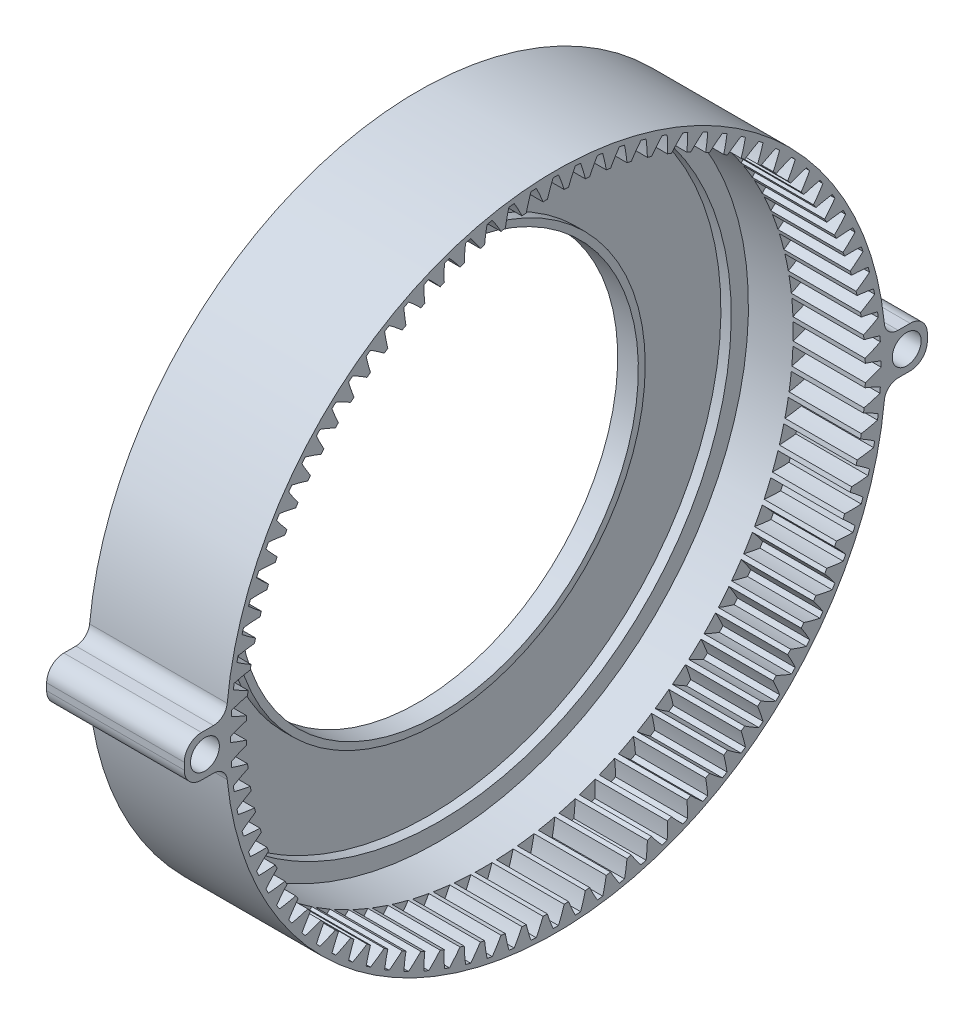
SolidWorks part; units mm, degrees
ref_plane "Front Plane" through (0, 0, 0) normal (0, 0, 1) x (1, 0, 0)
ref_plane "Top Plane" through (0, 0, 0) normal (0, 1, 0) x (1, 0, 0)
ref_plane "Right Plane" through (0, 0, 0) normal (1, 0, 0) x (0, 0, -1)
ref_plane "Plane1" through (0, 0, 0) normal (0, 0, -1) x (-1, 0, 0)
sketch "Sketch1" plane through (0, 0, 0) normal (0, 0, -1) x (-1, 0, 0)
  line L0 (-20, 48) -> (-20, 0)
  line L1 (-20, 0) -> (0, 0)
  line L2 (0, 0) -> (0, 48)
  line L3 (0, 48) -> (-20, 48)
  line L4 (-20, 0) -> (0, 0) construction
  dimension "D1" = 48
  dimension "D2" = 20
revolve "Revolve1" add sketch "Sketch1" angle 360 about L4 reverse direction yes
sketch "Sketch2" plane through (20, 0, 0) normal (1, 0, 0) x (0, 0, -1)
  arc A0 (-4.9202, -44.7302) -> (-4.2833, -44.7957) centre (0, 0) ccw
  arc A1 (-4.2833, -44.7957) -> (-3.6099, -47.1129) centre (18.1092, -39.5446) ccw
  arc A2 (-3.6099, -47.1129) -> (-2.8389, -47.1656) centre (0, 0) ccw
  arc A3 (-2.8389, -47.1656) -> (-1.8563, -44.9617) centre (-23.3252, -36.7104) ccw
  arc A4 (-1.8563, -44.9617) -> (-1.2163, -44.9836) centre (0, 0) ccw
  arc A5 (-1.2163, -44.9836) -> (-0.3864, -47.2494) centre (20.7656, -38.2166) ccw
  arc A6 (-0.3864, -47.2494) -> (0.3864, -47.2494) centre (0, 0) ccw
  arc A7 (0.3864, -47.2494) -> (1.2163, -44.9836) centre (-20.7656, -38.2166) ccw
  arc A8 (1.2163, -44.9836) -> (1.8563, -44.9617) centre (0, 0) ccw
  arc A9 (1.8563, -44.9617) -> (2.8389, -47.1656) centre (23.3252, -36.7104) ccw
  arc A10 (2.8389, -47.1656) -> (3.6099, -47.1129) centre (0, 0) ccw
  arc A11 (3.6099, -47.1129) -> (4.2833, -44.7957) centre (-18.1092, -39.5446) ccw
  arc A12 (4.2833, -44.7957) -> (4.9202, -44.7302) centre (0, 0) ccw
  arc A13 (4.9202, -44.7302) -> (6.051, -46.8619) centre (25.7761, -35.0331) ccw
  arc A14 (6.051, -46.8619) -> (6.8166, -46.7567) centre (0, 0) ccw
  arc A15 (6.8166, -46.7567) -> (7.3303, -44.399) centre (-15.3684, -40.6882) ccw
  arc A16 (7.3303, -44.399) -> (7.9613, -44.2902) centre (0, 0) ccw
  arc A17 (7.9613, -44.2902) -> (9.2349, -46.3398) centre (28.1067, -33.1924) ccw
  arc A18 (9.2349, -46.3398) -> (9.9915, -46.1825) centre (0, 0) ccw
  arc A19 (9.9915, -46.1825) -> (10.3431, -43.7952) centre (-12.5559, -41.6422) ccw
  arc A20 (10.3431, -43.7952) -> (10.9652, -43.6436) centre (0, 0) ccw
  arc A21 (10.9652, -43.6436) -> (12.3757, -45.6015) centre (30.3063, -31.1969) ccw
  arc A22 (12.3757, -45.6015) -> (13.1198, -45.393) centre (0, 0) ccw
  arc A23 (13.1198, -45.393) -> (13.3077, -42.9873) centre (-9.6849, -42.4019) ccw
  arc A24 (13.3077, -42.9873) -> (13.918, -42.7936) centre (0, 0) ccw
  arc A25 (13.918, -42.7936) -> (15.4588, -44.6507) centre (32.3646, -29.056) ccw
  arc A26 (15.4588, -44.6507) -> (16.1869, -44.3919) centre (0, 0) ccw
  arc A27 (16.1869, -44.3919) -> (16.2102, -41.9789) centre (-6.7687, -42.964) ccw
  arc A28 (16.2102, -41.9789) -> (16.8058, -41.744) centre (0, 0) ccw
  arc A29 (16.8058, -41.744) -> (18.4698, -43.4916) centre (34.272, -26.7796) ccw
  arc A30 (18.4698, -43.4916) -> (19.1786, -43.1838) centre (0, 0) ccw
  arc A31 (19.1786, -43.1838) -> (19.0371, -40.7748) centre (-3.821, -43.3257) ccw
  arc A32 (19.0371, -40.7748) -> (19.6154, -40.4998) centre (0, 0) ccw
  arc A33 (19.6154, -40.4998) -> (21.3948, -42.1298) centre (36.0196, -24.3784) ccw
  arc A34 (21.3948, -42.1298) -> (22.0809, -41.7743) centre (0, 0) ccw
  arc A35 (22.0809, -41.7743) -> (21.7753, -39.3806) centre (-0.8554, -43.4855) ccw
  arc A36 (21.7753, -39.3806) -> (22.3335, -39.0668) centre (0, 0) ccw
  arc A37 (22.3335, -39.0668) -> (24.2199, -40.5716) centre (37.5993, -21.8635) ccw
  arc A38 (24.2199, -40.5716) -> (24.8802, -40.1701) centre (0, 0) ccw
  arc A39 (24.8802, -40.1701) -> (24.412, -37.8028) centre (2.1142, -43.4425) ccw
  arc A40 (24.412, -37.8028) -> (24.9474, -37.4517) centre (0, 0) ccw
  arc A41 (24.9474, -37.4517) -> (26.9322, -38.8242) centre (39.0037, -19.2467) ccw
  arc A42 (26.9322, -38.8242) -> (27.5635, -38.3785) centre (0, 0) ccw
  arc A43 (27.5635, -38.3785) -> (26.9349, -36.0488) centre (5.0738, -43.1969) ccw
  arc A44 (26.9349, -36.0488) -> (27.445, -35.6619) centre (0, 0) ccw
  arc A45 (27.445, -35.6619) -> (29.5188, -36.8957) centre (40.2262, -16.5401) ccw
  arc A46 (29.5188, -36.8957) -> (30.1183, -36.4081) centre (0, 0) ccw
  arc A47 (30.1183, -36.4081) -> (29.3321, -34.1266) centre (8.0099, -42.75) ccw
  arc A48 (29.3321, -34.1266) -> (29.8147, -33.7058) centre (0, 0) ccw
  arc A49 (29.8147, -33.7058) -> (31.9679, -34.7953) centre (41.2611, -13.7564) ccw
  arc A50 (31.9679, -34.7953) -> (32.5326, -34.2679) centre (0, 0) ccw
  arc A51 (32.5326, -34.2679) -> (31.5926, -32.0454) centre (10.9086, -42.1037) ccw
  arc A52 (31.5926, -32.0454) -> (32.0454, -31.5926) centre (0, 0) ccw
  arc A53 (32.0454, -31.5926) -> (34.2679, -32.5326) centre (42.1037, -10.9086) ccw
  arc A54 (34.2679, -32.5326) -> (34.7953, -31.9679) centre (0, 0) ccw
  arc A55 (34.7953, -31.9679) -> (33.7058, -29.8147) centre (13.7564, -41.2611) ccw
  arc A56 (33.7058, -29.8147) -> (34.1266, -29.3321) centre (0, 0) ccw
  arc A57 (34.1266, -29.3321) -> (36.4081, -30.1183) centre (42.75, -8.0099) ccw
  arc A58 (36.4081, -30.1183) -> (36.8957, -29.5188) centre (0, 0) ccw
  arc A59 (36.8957, -29.5188) -> (35.6619, -27.445) centre (16.5401, -40.2262) ccw
  arc A60 (35.6619, -27.445) -> (36.0488, -26.9349) centre (0, 0) ccw
  arc A61 (36.0488, -26.9349) -> (38.3785, -27.5635) centre (43.1969, -5.0738) ccw
  arc A62 (38.3785, -27.5635) -> (38.8242, -26.9322) centre (0, 0) ccw
  arc A63 (38.8242, -26.9322) -> (37.4517, -24.9474) centre (19.2467, -39.0037) ccw
  arc A64 (37.4517, -24.9474) -> (37.8028, -24.412) centre (0, 0) ccw
  arc A65 (37.8028, -24.412) -> (40.1701, -24.8802) centre (43.4425, -2.1142) ccw
  arc A66 (40.1701, -24.8802) -> (40.5716, -24.2199) centre (0, 0) ccw
  arc A67 (40.5716, -24.2199) -> (39.0668, -22.3335) centre (21.8635, -37.5993) ccw
  arc A68 (39.0668, -22.3335) -> (39.3806, -21.7753) centre (0, 0) ccw
  arc A69 (39.3806, -21.7753) -> (41.7743, -22.0809) centre (43.4855, 0.8554) ccw
  arc A70 (41.7743, -22.0809) -> (42.1298, -21.3948) centre (0, 0) ccw
  arc A71 (42.1298, -21.3948) -> (40.4998, -19.6154) centre (24.3784, -36.0196) ccw
  arc A72 (40.4998, -19.6154) -> (40.7748, -19.0371) centre (0, 0) ccw
  arc A73 (40.7748, -19.0371) -> (43.1838, -19.1786) centre (43.3257, 3.821) ccw
  arc A74 (43.1838, -19.1786) -> (43.4916, -18.4698) centre (0, 0) ccw
  arc A75 (43.4916, -18.4698) -> (41.744, -16.8058) centre (26.7796, -34.272) ccw
  arc A76 (41.744, -16.8058) -> (41.9789, -16.2102) centre (0, 0) ccw
  arc A77 (41.9789, -16.2102) -> (44.3919, -16.1869) centre (42.964, 6.7687) ccw
  arc A78 (44.3919, -16.1869) -> (44.6507, -15.4588) centre (0, 0) ccw
  arc A79 (44.6507, -15.4588) -> (42.7936, -13.918) centre (29.056, -32.3646) ccw
  arc A80 (42.7936, -13.918) -> (42.9873, -13.3077) centre (0, 0) ccw
  arc A81 (42.9873, -13.3077) -> (45.393, -13.1198) centre (42.4019, 9.6849) ccw
  arc A82 (45.393, -13.1198) -> (45.6015, -12.3757) centre (0, 0) ccw
  arc A83 (45.6015, -12.3757) -> (43.6436, -10.9652) centre (31.1969, -30.3063) ccw
  arc A84 (43.6436, -10.9652) -> (43.7952, -10.3431) centre (0, 0) ccw
  arc A85 (43.7952, -10.3431) -> (46.1825, -9.9915) centre (41.6422, 12.5559) ccw
  arc A86 (46.1825, -9.9915) -> (46.3398, -9.2349) centre (0, 0) ccw
  arc A87 (46.3398, -9.2349) -> (44.2902, -7.9613) centre (33.1924, -28.1067) ccw
  arc A88 (44.2902, -7.9613) -> (44.399, -7.3303) centre (0, 0) ccw
  arc A89 (44.399, -7.3303) -> (46.7567, -6.8166) centre (40.6882, 15.3684) ccw
  arc A90 (46.7567, -6.8166) -> (46.8619, -6.051) centre (0, 0) ccw
  arc A91 (46.8619, -6.051) -> (44.7302, -4.9202) centre (35.0331, -25.7761) ccw
  arc A92 (44.7302, -4.9202) -> (44.7957, -4.2833) centre (0, 0) ccw
  arc A93 (44.7957, -4.2833) -> (47.1129, -3.6099) centre (39.5446, 18.1092) ccw
  arc A94 (47.1129, -3.6099) -> (47.1656, -2.8389) centre (0, 0) ccw
  arc A95 (47.1656, -2.8389) -> (44.9617, -1.8563) centre (36.7104, -23.3252) ccw
  arc A96 (44.9617, -1.8563) -> (44.9836, -1.2163) centre (0, 0) ccw
  arc A97 (44.9836, -1.2163) -> (47.2494, -0.3864) centre (38.2166, 20.7656) ccw
  arc A98 (47.2494, -0.3864) -> (47.2494, 0.3864) centre (0, 0) ccw
  arc A99 (47.2494, 0.3864) -> (44.9836, 1.2163) centre (38.2166, -20.7656) ccw
  arc A100 (44.9836, 1.2163) -> (44.9617, 1.8563) centre (0, 0) ccw
  arc A101 (44.9617, 1.8563) -> (47.1656, 2.8389) centre (36.7104, 23.3252) ccw
  arc A102 (47.1656, 2.8389) -> (47.1129, 3.6099) centre (0, 0) ccw
  arc A103 (47.1129, 3.6099) -> (44.7957, 4.2833) centre (39.5446, -18.1092) ccw
  arc A104 (44.7957, 4.2833) -> (44.7302, 4.9202) centre (0, 0) ccw
  arc A105 (44.7302, 4.9202) -> (46.8619, 6.051) centre (35.0331, 25.7761) ccw
  arc A106 (46.8619, 6.051) -> (46.7567, 6.8166) centre (0, 0) ccw
  arc A107 (46.7567, 6.8166) -> (44.399, 7.3303) centre (40.6882, -15.3684) ccw
  arc A108 (44.399, 7.3303) -> (44.2902, 7.9613) centre (0, 0) ccw
  arc A109 (44.2902, 7.9613) -> (46.3398, 9.2349) centre (33.1924, 28.1067) ccw
  arc A110 (46.3398, 9.2349) -> (46.1825, 9.9915) centre (0, 0) ccw
  arc A111 (46.1825, 9.9915) -> (43.7952, 10.3431) centre (41.6422, -12.5559) ccw
  arc A112 (43.7952, 10.3431) -> (43.6436, 10.9652) centre (0, 0) ccw
  arc A113 (43.6436, 10.9652) -> (45.6015, 12.3757) centre (31.1969, 30.3063) ccw
  arc A114 (45.6015, 12.3757) -> (45.393, 13.1198) centre (0, 0) ccw
  arc A115 (45.393, 13.1198) -> (42.9873, 13.3077) centre (42.4019, -9.6849) ccw
  arc A116 (42.9873, 13.3077) -> (42.7936, 13.918) centre (0, 0) ccw
  arc A117 (42.7936, 13.918) -> (44.6507, 15.4588) centre (29.056, 32.3646) ccw
  arc A118 (44.6507, 15.4588) -> (44.3919, 16.1869) centre (0, 0) ccw
  arc A119 (44.3919, 16.1869) -> (41.9789, 16.2102) centre (42.964, -6.7687) ccw
  arc A120 (41.9789, 16.2102) -> (41.744, 16.8058) centre (0, 0) ccw
  arc A121 (41.744, 16.8058) -> (43.4916, 18.4698) centre (26.7796, 34.272) ccw
  arc A122 (43.4916, 18.4698) -> (43.1838, 19.1786) centre (0, 0) ccw
  arc A123 (43.1838, 19.1786) -> (40.7748, 19.0371) centre (43.3257, -3.821) ccw
  arc A124 (40.7748, 19.0371) -> (40.4998, 19.6154) centre (0, 0) ccw
  arc A125 (40.4998, 19.6154) -> (42.1298, 21.3948) centre (24.3784, 36.0196) ccw
  arc A126 (42.1298, 21.3948) -> (41.7743, 22.0809) centre (0, 0) ccw
  arc A127 (41.7743, 22.0809) -> (39.3806, 21.7753) centre (43.4855, -0.8554) ccw
  arc A128 (39.3806, 21.7753) -> (39.0668, 22.3335) centre (0, 0) ccw
  arc A129 (39.0668, 22.3335) -> (40.5716, 24.2199) centre (21.8635, 37.5993) ccw
  arc A130 (40.5716, 24.2199) -> (40.1701, 24.8802) centre (0, 0) ccw
  arc A131 (40.1701, 24.8802) -> (37.8028, 24.412) centre (43.4425, 2.1142) ccw
  arc A132 (37.8028, 24.412) -> (37.4517, 24.9474) centre (0, 0) ccw
  arc A133 (37.4517, 24.9474) -> (38.8242, 26.9322) centre (19.2467, 39.0037) ccw
  arc A134 (38.8242, 26.9322) -> (38.3785, 27.5635) centre (0, 0) ccw
  arc A135 (38.3785, 27.5635) -> (36.0488, 26.9349) centre (43.1969, 5.0738) ccw
  arc A136 (36.0488, 26.9349) -> (35.6619, 27.445) centre (0, 0) ccw
  arc A137 (35.6619, 27.445) -> (36.8957, 29.5188) centre (16.5401, 40.2262) ccw
  arc A138 (36.8957, 29.5188) -> (36.4081, 30.1183) centre (0, 0) ccw
  arc A139 (36.4081, 30.1183) -> (34.1266, 29.3321) centre (42.75, 8.0099) ccw
  arc A140 (34.1266, 29.3321) -> (33.7058, 29.8147) centre (0, 0) ccw
  arc A141 (33.7058, 29.8147) -> (34.7953, 31.9679) centre (13.7564, 41.2611) ccw
  arc A142 (34.7953, 31.9679) -> (34.2679, 32.5326) centre (0, 0) ccw
  arc A143 (34.2679, 32.5326) -> (32.0454, 31.5926) centre (42.1037, 10.9086) ccw
  arc A144 (32.0454, 31.5926) -> (31.5926, 32.0454) centre (0, 0) ccw
  arc A145 (31.5926, 32.0454) -> (32.5326, 34.2679) centre (10.9086, 42.1037) ccw
  arc A146 (32.5326, 34.2679) -> (31.9679, 34.7953) centre (0, 0) ccw
  arc A147 (31.9679, 34.7953) -> (29.8147, 33.7058) centre (41.2611, 13.7564) ccw
  arc A148 (29.8147, 33.7058) -> (29.3321, 34.1266) centre (0, 0) ccw
  arc A149 (29.3321, 34.1266) -> (30.1183, 36.4081) centre (8.0099, 42.75) ccw
  arc A150 (30.1183, 36.4081) -> (29.5188, 36.8957) centre (0, 0) ccw
  arc A151 (29.5188, 36.8957) -> (27.445, 35.6619) centre (40.2262, 16.5401) ccw
  arc A152 (27.445, 35.6619) -> (26.9349, 36.0488) centre (0, 0) ccw
  arc A153 (26.9349, 36.0488) -> (27.5635, 38.3785) centre (5.0738, 43.1969) ccw
  arc A154 (27.5635, 38.3785) -> (26.9322, 38.8242) centre (0, 0) ccw
  arc A155 (26.9322, 38.8242) -> (24.9474, 37.4517) centre (39.0037, 19.2467) ccw
  arc A156 (24.9474, 37.4517) -> (24.412, 37.8028) centre (0, 0) ccw
  arc A157 (24.412, 37.8028) -> (24.8802, 40.1701) centre (2.1142, 43.4425) ccw
  arc A158 (24.8802, 40.1701) -> (24.2199, 40.5716) centre (0, 0) ccw
  arc A159 (24.2199, 40.5716) -> (22.3335, 39.0668) centre (37.5993, 21.8635) ccw
  arc A160 (22.3335, 39.0668) -> (21.7753, 39.3806) centre (0, 0) ccw
  arc A161 (21.7753, 39.3806) -> (22.0809, 41.7743) centre (-0.8554, 43.4855) ccw
  arc A162 (22.0809, 41.7743) -> (21.3948, 42.1298) centre (0, 0) ccw
  arc A163 (21.3948, 42.1298) -> (19.6154, 40.4998) centre (36.0196, 24.3784) ccw
  arc A164 (19.6154, 40.4998) -> (19.0371, 40.7748) centre (0, 0) ccw
  arc A165 (19.0371, 40.7748) -> (19.1786, 43.1838) centre (-3.821, 43.3257) ccw
  arc A166 (19.1786, 43.1838) -> (18.4698, 43.4916) centre (0, 0) ccw
  arc A167 (18.4698, 43.4916) -> (16.8058, 41.744) centre (34.272, 26.7796) ccw
  arc A168 (16.8058, 41.744) -> (16.2102, 41.9789) centre (0, 0) ccw
  arc A169 (16.2102, 41.9789) -> (16.1869, 44.3919) centre (-6.7687, 42.964) ccw
  arc A170 (16.1869, 44.3919) -> (15.4588, 44.6507) centre (0, 0) ccw
  arc A171 (15.4588, 44.6507) -> (13.918, 42.7936) centre (32.3646, 29.056) ccw
  arc A172 (13.918, 42.7936) -> (13.3077, 42.9873) centre (0, 0) ccw
  arc A173 (13.3077, 42.9873) -> (13.1198, 45.393) centre (-9.6849, 42.4019) ccw
  arc A174 (13.1198, 45.393) -> (12.3757, 45.6015) centre (0, 0) ccw
  arc A175 (12.3757, 45.6015) -> (10.9652, 43.6436) centre (30.3063, 31.1969) ccw
  arc A176 (10.9652, 43.6436) -> (10.3431, 43.7952) centre (0, 0) ccw
  arc A177 (10.3431, 43.7952) -> (9.9915, 46.1825) centre (-12.5559, 41.6422) ccw
  arc A178 (9.9915, 46.1825) -> (9.2349, 46.3398) centre (0, 0) ccw
  arc A179 (9.2349, 46.3398) -> (7.9613, 44.2902) centre (28.1067, 33.1924) ccw
  arc A180 (7.9613, 44.2902) -> (7.3303, 44.399) centre (0, 0) ccw
  arc A181 (7.3303, 44.399) -> (6.8166, 46.7567) centre (-15.3684, 40.6882) ccw
  arc A182 (6.8166, 46.7567) -> (6.051, 46.8619) centre (0, 0) ccw
  arc A183 (6.051, 46.8619) -> (4.9202, 44.7302) centre (25.7761, 35.0331) ccw
  arc A184 (4.9202, 44.7302) -> (4.2833, 44.7957) centre (0, 0) ccw
  arc A185 (4.2833, 44.7957) -> (3.6099, 47.1129) centre (-18.1092, 39.5446) ccw
  arc A186 (3.6099, 47.1129) -> (2.8389, 47.1656) centre (0, 0) ccw
  arc A187 (2.8389, 47.1656) -> (1.8563, 44.9617) centre (23.3252, 36.7104) ccw
  arc A188 (1.8563, 44.9617) -> (1.2163, 44.9836) centre (0, 0) ccw
  arc A189 (1.2163, 44.9836) -> (0.3864, 47.2494) centre (-20.7656, 38.2166) ccw
  arc A190 (0.3864, 47.2494) -> (-0.3864, 47.2494) centre (0, 0) ccw
  arc A191 (-0.3864, 47.2494) -> (-1.2163, 44.9836) centre (20.7656, 38.2166) ccw
  arc A192 (-1.2163, 44.9836) -> (-1.8563, 44.9617) centre (0, 0) ccw
  arc A193 (-1.8563, 44.9617) -> (-2.8389, 47.1656) centre (-23.3252, 36.7104) ccw
  arc A194 (-2.8389, 47.1656) -> (-3.6099, 47.1129) centre (0, 0) ccw
  arc A195 (-3.6099, 47.1129) -> (-4.2833, 44.7957) centre (18.1092, 39.5446) ccw
  arc A196 (-4.2833, 44.7957) -> (-4.9202, 44.7302) centre (0, 0) ccw
  arc A197 (-4.9202, 44.7302) -> (-6.051, 46.8619) centre (-25.7761, 35.0331) ccw
  arc A198 (-6.051, 46.8619) -> (-6.8166, 46.7567) centre (0, 0) ccw
  arc A199 (-6.8166, 46.7567) -> (-7.3303, 44.399) centre (15.3684, 40.6882) ccw
  arc A200 (-7.3303, 44.399) -> (-7.9613, 44.2902) centre (0, 0) ccw
  arc A201 (-7.9613, 44.2902) -> (-9.2349, 46.3398) centre (-28.1067, 33.1924) ccw
  arc A202 (-9.2349, 46.3398) -> (-9.9915, 46.1825) centre (0, 0) ccw
  arc A203 (-9.9915, 46.1825) -> (-10.3431, 43.7952) centre (12.5559, 41.6422) ccw
  arc A204 (-10.3431, 43.7952) -> (-10.9652, 43.6436) centre (0, 0) ccw
  arc A205 (-10.9652, 43.6436) -> (-12.3757, 45.6015) centre (-30.3063, 31.1969) ccw
  arc A206 (-12.3757, 45.6015) -> (-13.1198, 45.393) centre (0, 0) ccw
  arc A207 (-13.1198, 45.393) -> (-13.3077, 42.9873) centre (9.6849, 42.4019) ccw
  arc A208 (-13.3077, 42.9873) -> (-13.918, 42.7936) centre (0, 0) ccw
  arc A209 (-13.918, 42.7936) -> (-15.4588, 44.6507) centre (-32.3646, 29.056) ccw
  arc A210 (-15.4588, 44.6507) -> (-16.1869, 44.3919) centre (0, 0) ccw
  arc A211 (-16.1869, 44.3919) -> (-16.2102, 41.9789) centre (6.7687, 42.964) ccw
  arc A212 (-16.2102, 41.9789) -> (-16.8058, 41.744) centre (0, 0) ccw
  arc A213 (-16.8058, 41.744) -> (-18.4698, 43.4916) centre (-34.272, 26.7796) ccw
  arc A214 (-18.4698, 43.4916) -> (-19.1786, 43.1838) centre (0, 0) ccw
  arc A215 (-19.1786, 43.1838) -> (-19.0371, 40.7748) centre (3.821, 43.3257) ccw
  arc A216 (-19.0371, 40.7748) -> (-19.6154, 40.4998) centre (0, 0) ccw
  arc A217 (-19.6154, 40.4998) -> (-21.3948, 42.1298) centre (-36.0196, 24.3784) ccw
  arc A218 (-21.3948, 42.1298) -> (-22.0809, 41.7743) centre (0, 0) ccw
  arc A219 (-22.0809, 41.7743) -> (-21.7753, 39.3806) centre (0.8554, 43.4855) ccw
  arc A220 (-21.7753, 39.3806) -> (-22.3335, 39.0668) centre (0, 0) ccw
  arc A221 (-22.3335, 39.0668) -> (-24.2199, 40.5716) centre (-37.5993, 21.8635) ccw
  arc A222 (-24.2199, 40.5716) -> (-24.8802, 40.1701) centre (0, 0) ccw
  arc A223 (-24.8802, 40.1701) -> (-24.412, 37.8028) centre (-2.1142, 43.4425) ccw
  arc A224 (-24.412, 37.8028) -> (-24.9474, 37.4517) centre (0, 0) ccw
  arc A225 (-24.9474, 37.4517) -> (-26.9322, 38.8242) centre (-39.0037, 19.2467) ccw
  arc A226 (-26.9322, 38.8242) -> (-27.5635, 38.3785) centre (0, 0) ccw
  arc A227 (-27.5635, 38.3785) -> (-26.9349, 36.0488) centre (-5.0738, 43.1969) ccw
  arc A228 (-26.9349, 36.0488) -> (-27.445, 35.6619) centre (0, 0) ccw
  arc A229 (-27.445, 35.6619) -> (-29.5188, 36.8957) centre (-40.2262, 16.5401) ccw
  arc A230 (-29.5188, 36.8957) -> (-30.1183, 36.4081) centre (0, 0) ccw
  arc A231 (-30.1183, 36.4081) -> (-29.3321, 34.1266) centre (-8.0099, 42.75) ccw
  arc A232 (-29.3321, 34.1266) -> (-29.8147, 33.7058) centre (0, 0) ccw
  arc A233 (-29.8147, 33.7058) -> (-31.9679, 34.7953) centre (-41.2611, 13.7564) ccw
  arc A234 (-31.9679, 34.7953) -> (-32.5326, 34.2679) centre (0, 0) ccw
  arc A235 (-32.5326, 34.2679) -> (-31.5926, 32.0454) centre (-10.9086, 42.1037) ccw
  arc A236 (-31.5926, 32.0454) -> (-32.0454, 31.5926) centre (0, 0) ccw
  arc A237 (-32.0454, 31.5926) -> (-34.2679, 32.5326) centre (-42.1037, 10.9086) ccw
  arc A238 (-34.2679, 32.5326) -> (-34.7953, 31.9679) centre (0, 0) ccw
  arc A239 (-34.7953, 31.9679) -> (-33.7058, 29.8147) centre (-13.7564, 41.2611) ccw
  arc A240 (-33.7058, 29.8147) -> (-34.1266, 29.3321) centre (0, 0) ccw
  arc A241 (-34.1266, 29.3321) -> (-36.4081, 30.1183) centre (-42.75, 8.0099) ccw
  arc A242 (-36.4081, 30.1183) -> (-36.8957, 29.5188) centre (0, 0) ccw
  arc A243 (-36.8957, 29.5188) -> (-35.6619, 27.445) centre (-16.5401, 40.2262) ccw
  arc A244 (-35.6619, 27.445) -> (-36.0488, 26.9349) centre (0, 0) ccw
  arc A245 (-36.0488, 26.9349) -> (-38.3785, 27.5635) centre (-43.1969, 5.0738) ccw
  arc A246 (-38.3785, 27.5635) -> (-38.8242, 26.9322) centre (0, 0) ccw
  arc A247 (-38.8242, 26.9322) -> (-37.4517, 24.9474) centre (-19.2467, 39.0037) ccw
  arc A248 (-37.4517, 24.9474) -> (-37.8028, 24.412) centre (0, 0) ccw
  arc A249 (-37.8028, 24.412) -> (-40.1701, 24.8802) centre (-43.4425, 2.1142) ccw
  arc A250 (-40.1701, 24.8802) -> (-40.5716, 24.2199) centre (0, 0) ccw
  arc A251 (-40.5716, 24.2199) -> (-39.0668, 22.3335) centre (-21.8635, 37.5993) ccw
  arc A252 (-39.0668, 22.3335) -> (-39.3806, 21.7753) centre (0, 0) ccw
  arc A253 (-39.3806, 21.7753) -> (-41.7743, 22.0809) centre (-43.4855, -0.8554) ccw
  arc A254 (-41.7743, 22.0809) -> (-42.1298, 21.3948) centre (0, 0) ccw
  arc A255 (-42.1298, 21.3948) -> (-40.4998, 19.6154) centre (-24.3784, 36.0196) ccw
  arc A256 (-40.4998, 19.6154) -> (-40.7748, 19.0371) centre (0, 0) ccw
  arc A257 (-40.7748, 19.0371) -> (-43.1838, 19.1786) centre (-43.3257, -3.821) ccw
  arc A258 (-43.1838, 19.1786) -> (-43.4916, 18.4698) centre (0, 0) ccw
  arc A259 (-43.4916, 18.4698) -> (-41.744, 16.8058) centre (-26.7796, 34.272) ccw
  arc A260 (-41.744, 16.8058) -> (-41.9789, 16.2102) centre (0, 0) ccw
  arc A261 (-41.9789, 16.2102) -> (-44.3919, 16.1869) centre (-42.964, -6.7687) ccw
  arc A262 (-44.3919, 16.1869) -> (-44.6507, 15.4588) centre (0, 0) ccw
  arc A263 (-44.6507, 15.4588) -> (-42.7936, 13.918) centre (-29.056, 32.3646) ccw
  arc A264 (-42.7936, 13.918) -> (-42.9873, 13.3077) centre (0, 0) ccw
  arc A265 (-42.9873, 13.3077) -> (-45.393, 13.1198) centre (-42.4019, -9.6849) ccw
  arc A266 (-45.393, 13.1198) -> (-45.6015, 12.3757) centre (0, 0) ccw
  arc A267 (-45.6015, 12.3757) -> (-43.6436, 10.9652) centre (-31.1969, 30.3063) ccw
  arc A268 (-43.6436, 10.9652) -> (-43.7952, 10.3431) centre (0, 0) ccw
  arc A269 (-43.7952, 10.3431) -> (-46.1825, 9.9915) centre (-41.6422, -12.5559) ccw
  arc A270 (-46.1825, 9.9915) -> (-46.3398, 9.2349) centre (0, 0) ccw
  arc A271 (-46.3398, 9.2349) -> (-44.2902, 7.9613) centre (-33.1924, 28.1067) ccw
  arc A272 (-44.2902, 7.9613) -> (-44.399, 7.3303) centre (0, 0) ccw
  arc A273 (-44.399, 7.3303) -> (-46.7567, 6.8166) centre (-40.6882, -15.3684) ccw
  arc A274 (-46.7567, 6.8166) -> (-46.8619, 6.051) centre (0, 0) ccw
  arc A275 (-46.8619, 6.051) -> (-44.7302, 4.9202) centre (-35.0331, 25.7761) ccw
  arc A276 (-44.7302, 4.9202) -> (-44.7957, 4.2833) centre (0, 0) ccw
  arc A277 (-44.7957, 4.2833) -> (-47.1129, 3.6099) centre (-39.5446, -18.1092) ccw
  arc A278 (-47.1129, 3.6099) -> (-47.1656, 2.8389) centre (0, 0) ccw
  arc A279 (-47.1656, 2.8389) -> (-44.9617, 1.8563) centre (-36.7104, 23.3252) ccw
  arc A280 (-44.9617, 1.8563) -> (-44.9836, 1.2163) centre (0, 0) ccw
  arc A281 (-44.9836, 1.2163) -> (-47.2494, 0.3864) centre (-38.2166, -20.7656) ccw
  arc A282 (-47.2494, 0.3864) -> (-47.2494, -0.3864) centre (0, 0) ccw
  arc A283 (-47.2494, -0.3864) -> (-44.9836, -1.2163) centre (-38.2166, 20.7656) ccw
  arc A284 (-44.9836, -1.2163) -> (-44.9617, -1.8563) centre (0, 0) ccw
  arc A285 (-44.9617, -1.8563) -> (-47.1656, -2.8389) centre (-36.7104, -23.3252) ccw
  arc A286 (-47.1656, -2.8389) -> (-47.1129, -3.6099) centre (0, 0) ccw
  arc A287 (-47.1129, -3.6099) -> (-44.7957, -4.2833) centre (-39.5446, 18.1092) ccw
  arc A288 (-44.7957, -4.2833) -> (-44.7302, -4.9202) centre (0, 0) ccw
  arc A289 (-44.7302, -4.9202) -> (-46.8619, -6.051) centre (-35.0331, -25.7761) ccw
  arc A290 (-46.8619, -6.051) -> (-46.7567, -6.8166) centre (0, 0) ccw
  arc A291 (-46.7567, -6.8166) -> (-44.399, -7.3303) centre (-40.6882, 15.3684) ccw
  arc A292 (-44.399, -7.3303) -> (-44.2902, -7.9613) centre (0, 0) ccw
  arc A293 (-44.2902, -7.9613) -> (-46.3398, -9.2349) centre (-33.1924, -28.1067) ccw
  arc A294 (-46.3398, -9.2349) -> (-46.1825, -9.9915) centre (0, 0) ccw
  arc A295 (-46.1825, -9.9915) -> (-43.7952, -10.3431) centre (-41.6422, 12.5559) ccw
  arc A296 (-43.7952, -10.3431) -> (-43.6436, -10.9652) centre (0, 0) ccw
  arc A297 (-43.6436, -10.9652) -> (-45.6015, -12.3757) centre (-31.1969, -30.3063) ccw
  arc A298 (-45.6015, -12.3757) -> (-45.393, -13.1198) centre (0, 0) ccw
  arc A299 (-45.393, -13.1198) -> (-42.9873, -13.3077) centre (-42.4019, 9.6849) ccw
  arc A300 (-42.9873, -13.3077) -> (-42.7936, -13.918) centre (0, 0) ccw
  arc A301 (-42.7936, -13.918) -> (-44.6507, -15.4588) centre (-29.056, -32.3646) ccw
  arc A302 (-44.6507, -15.4588) -> (-44.3919, -16.1869) centre (0, 0) ccw
  arc A303 (-44.3919, -16.1869) -> (-41.9789, -16.2102) centre (-42.964, 6.7687) ccw
  arc A304 (-41.9789, -16.2102) -> (-41.744, -16.8058) centre (0, 0) ccw
  arc A305 (-41.744, -16.8058) -> (-43.4916, -18.4698) centre (-26.7796, -34.272) ccw
  arc A306 (-43.4916, -18.4698) -> (-43.1838, -19.1786) centre (0, 0) ccw
  arc A307 (-43.1838, -19.1786) -> (-40.7748, -19.0371) centre (-43.3257, 3.821) ccw
  arc A308 (-40.7748, -19.0371) -> (-40.4998, -19.6154) centre (0, 0) ccw
  arc A309 (-40.4998, -19.6154) -> (-42.1298, -21.3948) centre (-24.3784, -36.0196) ccw
  arc A310 (-42.1298, -21.3948) -> (-41.7743, -22.0809) centre (0, 0) ccw
  arc A311 (-41.7743, -22.0809) -> (-39.3806, -21.7753) centre (-43.4855, 0.8554) ccw
  arc A312 (-39.3806, -21.7753) -> (-39.0668, -22.3335) centre (0, 0) ccw
  arc A313 (-39.0668, -22.3335) -> (-40.5716, -24.2199) centre (-21.8635, -37.5993) ccw
  arc A314 (-40.5716, -24.2199) -> (-40.1701, -24.8802) centre (0, 0) ccw
  arc A315 (-40.1701, -24.8802) -> (-37.8028, -24.412) centre (-43.4425, -2.1142) ccw
  arc A316 (-37.8028, -24.412) -> (-37.4517, -24.9474) centre (0, 0) ccw
  arc A317 (-37.4517, -24.9474) -> (-38.8242, -26.9322) centre (-19.2467, -39.0037) ccw
  arc A318 (-38.8242, -26.9322) -> (-38.3785, -27.5635) centre (0, 0) ccw
  arc A319 (-38.3785, -27.5635) -> (-36.0488, -26.9349) centre (-43.1969, -5.0738) ccw
  arc A320 (-36.0488, -26.9349) -> (-35.6619, -27.445) centre (0, 0) ccw
  arc A321 (-35.6619, -27.445) -> (-36.8957, -29.5188) centre (-16.5401, -40.2262) ccw
  arc A322 (-36.8957, -29.5188) -> (-36.4081, -30.1183) centre (0, 0) ccw
  arc A323 (-36.4081, -30.1183) -> (-34.1266, -29.3321) centre (-42.75, -8.0099) ccw
  arc A324 (-34.1266, -29.3321) -> (-33.7058, -29.8147) centre (0, 0) ccw
  arc A325 (-33.7058, -29.8147) -> (-34.7953, -31.9679) centre (-13.7564, -41.2611) ccw
  arc A326 (-34.7953, -31.9679) -> (-34.2679, -32.5326) centre (0, 0) ccw
  arc A327 (-34.2679, -32.5326) -> (-32.0454, -31.5926) centre (-42.1037, -10.9086) ccw
  arc A328 (-32.0454, -31.5926) -> (-31.5926, -32.0454) centre (0, 0) ccw
  arc A329 (-31.5926, -32.0454) -> (-32.5326, -34.2679) centre (-10.9086, -42.1037) ccw
  arc A330 (-32.5326, -34.2679) -> (-31.9679, -34.7953) centre (0, 0) ccw
  arc A331 (-31.9679, -34.7953) -> (-29.8147, -33.7058) centre (-41.2611, -13.7564) ccw
  arc A332 (-29.8147, -33.7058) -> (-29.3321, -34.1266) centre (0, 0) ccw
  arc A333 (-29.3321, -34.1266) -> (-30.1183, -36.4081) centre (-8.0099, -42.75) ccw
  arc A334 (-30.1183, -36.4081) -> (-29.5188, -36.8957) centre (0, 0) ccw
  arc A335 (-29.5188, -36.8957) -> (-27.445, -35.6619) centre (-40.2262, -16.5401) ccw
  arc A336 (-27.445, -35.6619) -> (-26.9349, -36.0488) centre (0, 0) ccw
  arc A337 (-26.9349, -36.0488) -> (-27.5635, -38.3785) centre (-5.0738, -43.1969) ccw
  arc A338 (-27.5635, -38.3785) -> (-26.9322, -38.8242) centre (0, 0) ccw
  arc A339 (-26.9322, -38.8242) -> (-24.9474, -37.4517) centre (-39.0037, -19.2467) ccw
  arc A340 (-24.9474, -37.4517) -> (-24.412, -37.8028) centre (0, 0) ccw
  arc A341 (-24.412, -37.8028) -> (-24.8802, -40.1701) centre (-2.1142, -43.4425) ccw
  arc A342 (-24.8802, -40.1701) -> (-24.2199, -40.5716) centre (0, 0) ccw
  arc A343 (-24.2199, -40.5716) -> (-22.3335, -39.0668) centre (-37.5993, -21.8635) ccw
  arc A344 (-22.3335, -39.0668) -> (-21.7753, -39.3806) centre (0, 0) ccw
  arc A345 (-21.7753, -39.3806) -> (-22.0809, -41.7743) centre (0.8554, -43.4855) ccw
  arc A346 (-22.0809, -41.7743) -> (-21.3948, -42.1298) centre (0, 0) ccw
  arc A347 (-21.3948, -42.1298) -> (-19.6154, -40.4998) centre (-36.0196, -24.3784) ccw
  arc A348 (-19.6154, -40.4998) -> (-19.0371, -40.7748) centre (0, 0) ccw
  arc A349 (-19.0371, -40.7748) -> (-19.1786, -43.1838) centre (3.821, -43.3257) ccw
  arc A350 (-19.1786, -43.1838) -> (-18.4698, -43.4916) centre (0, 0) ccw
  arc A351 (-18.4698, -43.4916) -> (-16.8058, -41.744) centre (-34.272, -26.7796) ccw
  arc A352 (-16.8058, -41.744) -> (-16.2102, -41.9789) centre (0, 0) ccw
  arc A353 (-16.2102, -41.9789) -> (-16.1869, -44.3919) centre (6.7687, -42.964) ccw
  arc A354 (-16.1869, -44.3919) -> (-15.4588, -44.6507) centre (0, 0) ccw
  arc A355 (-15.4588, -44.6507) -> (-13.918, -42.7936) centre (-32.3646, -29.056) ccw
  arc A356 (-13.918, -42.7936) -> (-13.3077, -42.9873) centre (0, 0) ccw
  arc A357 (-13.3077, -42.9873) -> (-13.1198, -45.393) centre (9.6849, -42.4019) ccw
  arc A358 (-13.1198, -45.393) -> (-12.3757, -45.6015) centre (0, 0) ccw
  arc A359 (-12.3757, -45.6015) -> (-10.9652, -43.6436) centre (-30.3063, -31.1969) ccw
  arc A360 (-10.9652, -43.6436) -> (-10.3431, -43.7952) centre (0, 0) ccw
  arc A361 (-10.3431, -43.7952) -> (-9.9915, -46.1825) centre (12.5559, -41.6422) ccw
  arc A362 (-9.9915, -46.1825) -> (-9.2349, -46.3398) centre (0, 0) ccw
  arc A363 (-9.2349, -46.3398) -> (-7.9613, -44.2902) centre (-28.1067, -33.1924) ccw
  arc A364 (-7.9613, -44.2902) -> (-7.3303, -44.399) centre (0, 0) ccw
  arc A365 (-7.3303, -44.399) -> (-6.8166, -46.7567) centre (15.3684, -40.6882) ccw
  arc A366 (-6.8166, -46.7567) -> (-6.051, -46.8619) centre (0, 0) ccw
  arc A367 (-6.051, -46.8619) -> (-4.9202, -44.7302) centre (-25.7761, -35.0331) ccw
extrude "Cut-Extrude1" cut sketch "Sketch2" against normal offset from surface (17 mm away) 3 up to face at (0, -48, 0)
hole_wizard "M52 Clearance Hole1" positions "Sketch4" profile "Sketch3" hole size "M52" standard "ANSI Metric"
sketch "Sketch4" plane through (0, 0, 0) normal (-1, 0, 0) x (0, 0, 1)
  point P0 (0, 0)
sketch "Sketch3" plane through (0, 0, 0) normal (0, 1, 0) x (0, 0, 1)
  line L0 (0, 0) -> (0, 20)
  line L1 (0, 20) -> (29, 20)
  line L2 (29, 20) -> (29, 0)
  line L5 (29, 0) -> (0, 0)
  line L11 (0, -6.35) -> (0, 107.95) construction
  dimension "Thru Hole Dia." = 58
  dimension "Thru Hole Depth" = 20
sketch "Sketch5" plane through (3, 0, 0) normal (-1, 0, 0) x (0, 0, 1)
  circle A0 centre (0, 0) radius 30
  circle A1 centre (0, 0) radius 42.5
  dimension "D1" = 60
  dimension "D2" = 85
extrude "Cut-Extrude3" cut sketch "Sketch5" along normal blind 1.5
sketch "Sketch7" plane through (3, 0, 0) normal (1, 0, 0) x (0, 0, -1)
  circle A0 centre (0, 0) radius 48
  circle A1 centre (0, 0) radius 45
  dimension "D1" = 90
  dimension "D2" = 96
extrude "Boss-Extrude2" add sketch "Sketch7" along normal blind 6.5
sketch "Sketch8" plane through (0, 0, 0) normal (1, 0, 0) x (0, 0, -1)
  line L0 (-51, 0) -> (51, 0) construction
  line L1 (-54, -3) -> (54, -3)
  line L2 (-54, -3) -> (-54, 3)
  line L3 (-54, 3) -> (54, 3)
  line L4 (54, -3) -> (54, 3)
  line L5 (-54, -3) -> (54, 3) construction
  line L6 (-54, 3) -> (54, -3) construction
  line L7 (-3, 54) -> (3, 54)
  line L8 (-3, 54) -> (-3, -54)
  line L9 (-3, -54) -> (3, -54)
  line L10 (3, 54) -> (3, -54)
  line L11 (-3, 54) -> (3, -54) construction
  line L12 (-3, -54) -> (3, 54) construction
  line L13 (0, -51) -> (0, 51) construction
  circle A0 centre (0, 0) radius 48 construction
  circle A1 centre (0, 0) radius 48
  circle A2 centre (51, 0) radius 2.1
  circle A3 centre (0, 51) radius 2.1
  circle A4 centre (0, -51) radius 2.1
  circle A5 centre (-51, 0) radius 2.1
  point P0 (0, 0)
  point P6 (0, 0)
  point P20 (0, 0)
  point P22 (0, 0)
  dimension "D2" = 4.2
  dimension "D1" = 108
  dimension "D3" = 6
  dimension "D4" = 51
extrude "Boss-Extrude3" add sketch "Sketch8" along normal up to surface (20 mm away) contours A1 L1 L4 L3 A2 | A1 L3 L2 L1 A5 | A2 | A5 region at (0, 0, 53.9145) region at (0, -1.5034, -48.062) region at (0, 0, -51) region at (0, 0, 51) up to face at (20, 0, 0)
extrude "Cut-Extrude4" cut sketch "Sketch8<4>" against normal blind 5 from surface contours A5 | A2 starting at face at (20, 0, 0)
sketch "Sketch8<4>" plane through (0, 0, 0) normal (1, 0, 0) x (0, 0, -1) same geometry as "Sketch8"
fillet "Fillet1" radius 2.5 4 edges at (10, -3, 54) (10, 3, 54) (10, 3, -54) (10, -3, -54)
fillet "Fillet2" radius 2 4 edges at (10, -3, 47.9062) (10, 3, 47.9062) (10, 3, -47.9062) (10, -3, -47.9062)
